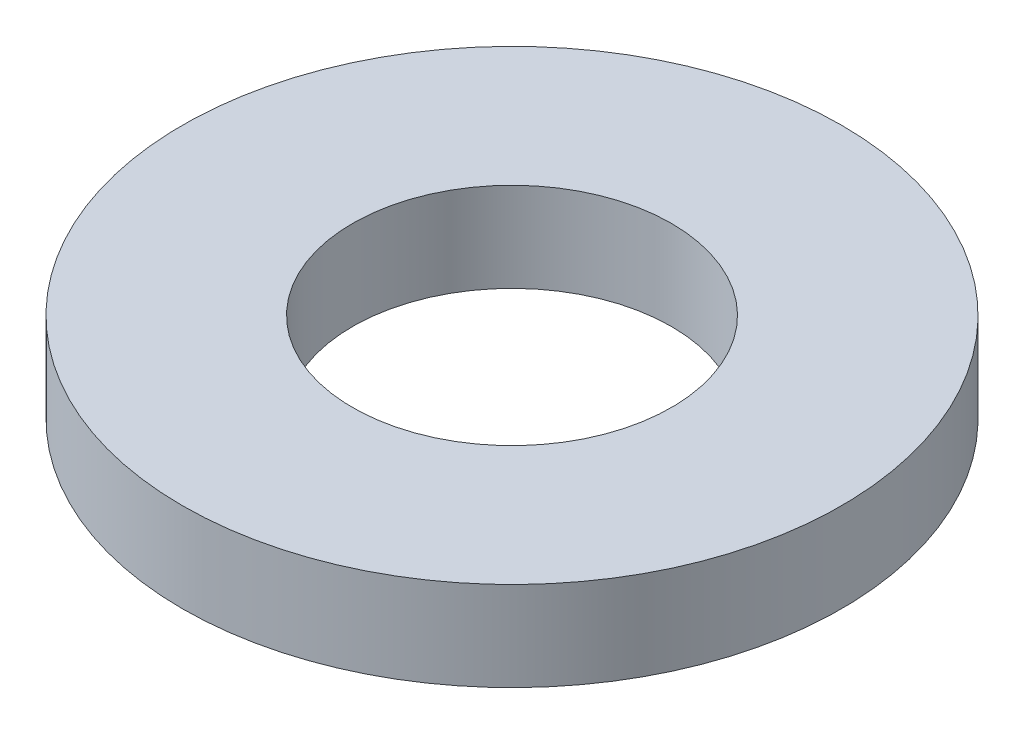
SolidWorks part; units mm, degrees
ref_plane "Front Plane" through (0, 0, 0) normal (0, 0, 1) x (1, 0, 0)
ref_plane "Top Plane" through (0, 0, 0) normal (0, 1, 0) x (1, 0, 0)
ref_plane "Right Plane" through (0, 0, 0) normal (1, 0, 0) x (0, 0, -1)
sketch "Sketch1" plane through (0, 0, 0) normal (0, 1, 0) x (1, 0, 0)
  circle A0 centre (0, 0) radius 77.5
  dimension "FLANGE_OD" = 155
extrude "Boss-Extrude1" add sketch "Sketch1" along normal blind 21
sketch "Sketch2" plane through (0, 0, 0) normal (0, 1, 0) x (1, 0, 0)
  circle A0 centre (0, 0) radius 37.5
  dimension "BORE_D" = 75
extrude "Cut-Extrude1" cut sketch "Sketch2" along normal through all
sketch "Sketch3" plane through (0, 21, 0) normal (0, 1, 0) x (1, 0, 0)
  circle A0 centre (0, 0) radius 24.5948 construction
  circle A1 centre (-24.5948, 0) radius 4.9471
  dimension "BOLT_D" = 9.8942
  dimension "BOLT_PCD" = 49.1896
extrude "Cut-Extrude2" cut sketch "Sketch3" against normal blind 19.4442 rebuild error yes
pattern_circular "CirPattern1" count 6 over 360 rebuild error yes
